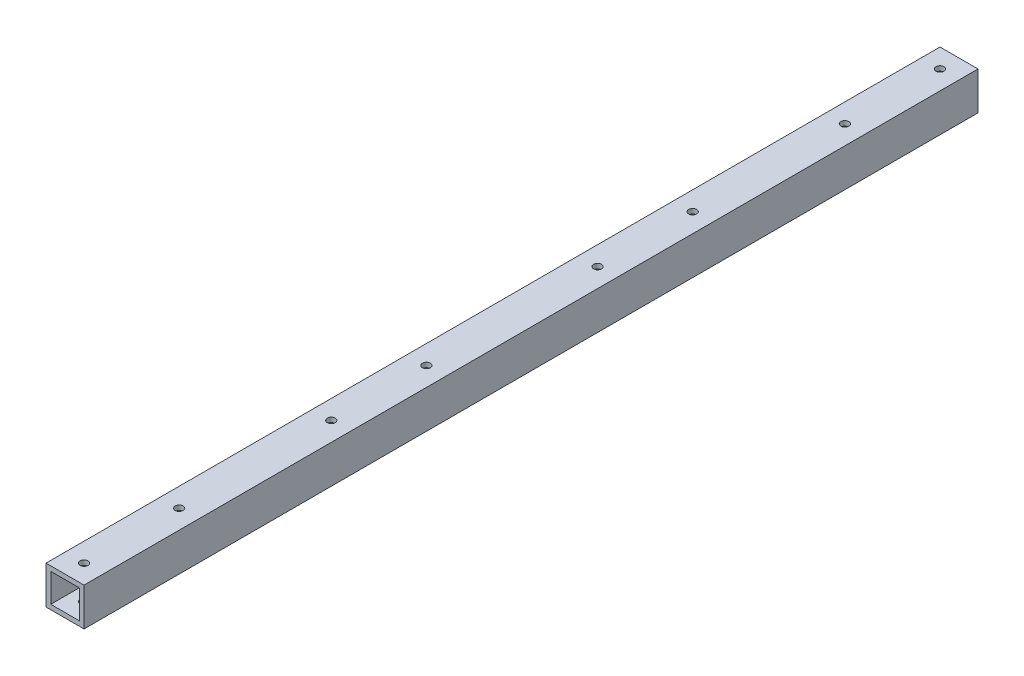
SolidWorks part; units mm, degrees
ref_plane "Front Plane" through (0, 0, 0) normal (0, 0, 1) x (1, 0, 0)
ref_plane "Top Plane" through (0, 0, 0) normal (0, 1, 0) x (1, 0, 0)
ref_plane "Right Plane" through (0, 0, 0) normal (1, 0, 0) x (0, 0, -1)
sketch "Sketch1" plane through (0, 0, 0) normal (0, 0, 1) x (1, 0, 0)
  line L0 (3.175, 22.225) -> (22.225, 22.225)
  line L1 (0, 0) -> (25.4, 0)
  line L2 (0, 0) -> (0, 25.4)
  line L3 (0, 25.4) -> (25.4, 25.4)
  line L4 (25.4, 0) -> (25.4, 25.4)
  line L5 (22.225, 3.175) -> (22.225, 22.225)
  line L6 (3.175, 3.175) -> (22.225, 3.175)
  line L7 (3.175, 3.175) -> (3.175, 22.225)
  dimension "D1" = 25.4
  dimension "D2" = 25.4
  dimension "D3" = 3.175
extrude "Boss-Extrude1" add sketch "Sketch1" along normal blind 596.9
sketch "Sketch2" plane through (0, 25.4, 0) normal (0, 1, 0) x (1, 0, 0)
  line L0 (25.4, -596.9) -> (25.4, 0) construction
  line L1 (25.4, -596.9) -> (0, -596.9) construction
  line L2 (0, -298.45) -> (25.4, -298.45) construction
  line L3 (0, -596.9) -> (0, 0) construction
  circle A0 centre (12.7, -584.2) radius 2.667
  circle A1 centre (12.7, -12.7) radius 2.667
  circle A2 centre (12.7, -520.7) radius 2.667
  circle A3 centre (12.7, -76.2) radius 2.667
  dimension "D1" = 5.334
  dimension "D4" = 5.334
  dimension "D2" = 12.7
  dimension "D3" = 12.7
  dimension "D5" = 12.7
  dimension "D6" = 63.5
extrude "Cut-Extrude1" cut sketch "Sketch2" against normal through all
sketch "Sketch4" plane through (0, 25.4, 0) normal (0, 1, 0) x (1, 0, 0)
  line L0 (0, -298.45) -> (25.4, -298.45) construction
  line L1 (0, -596.9) -> (0, 0) construction
  line L2 (25.4, -596.9) -> (25.4, 0) construction
  circle A0 centre (12.7, -419.1) radius 2.667
  circle A1 centre (12.7, -355.6) radius 2.667
  circle A2 centre (12.7, -520.7) radius 2.667 construction
  circle A4 centre (12.7, -177.8) radius 2.667
  circle A5 centre (12.7, -241.3) radius 2.667
  dimension "D1" = 101.6
  dimension "D2" = 63.5
  dimension "D5" = 5.334
  dimension "D6" = 5.334
  dimension "D3" = 12.7
  dimension "D4" = 12.7
extrude "Cut-Extrude3" cut sketch "Sketch4" against normal blind 25.4
